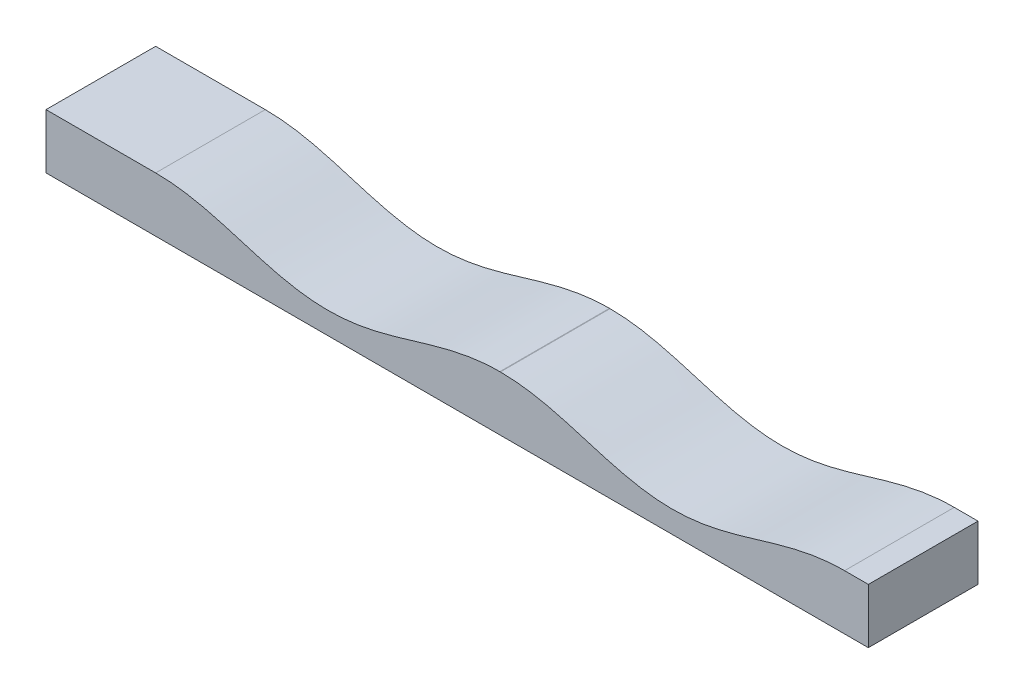
SolidWorks part; units mm, degrees
ref_plane "Front Plane" through (0, 0, 0) normal (0, 0, 1) x (1, 0, 0)
ref_plane "Top Plane" through (0, 0, 0) normal (0, 1, 0) x (1, 0, 0)
ref_plane "Right Plane" through (0, 0, 0) normal (1, 0, 0) x (0, 0, -1)
sketch "Sketch1" plane through (0, 0, 0) normal (0, 1, 0) x (1, 0, 0)
  line L1 (150, -10) -> (0, -10)
  line L2 (150, -10) -> (150, 10)
  line L3 (150, 10) -> (0, 10)
  line L4 (0, -10) -> (0, 10)
  line L5 (150, -10) -> (0, 10) construction
  line L6 (150, 10) -> (0, -10) construction
  point P0 (75, 0)
  point P5 (0, 0)
  dimension "D1" = 20
  dimension "D2" = 150
extrude "Boss-Extrude1" add sketch "Sketch1" along normal blind 10
sketch "Sketch2" plane through (0, 0, 0) normal (0, 0, 1) x (1, 0, 0)
  line L0 (0, 10) -> (20, 10) construction
  line L1 (20, 10) -> (145.6637, 10)
  spline S0 degree 4 poles (7.4336, 7.927) (7.8832, 8.0554) (8.7838, 8.3072) (10.1396, 8.6674) (11.7328, 9.0425) (13.1075, 9.3224) (14.3551, 9.5403) (15.3091, 9.6816) (16.199, 9.7903) (17.0227, 9.8706) (17.6834, 9.9225) (18.2645, 9.9568) (18.7489, 9.9781) (19.1768, 9.9904) (19.5397, 9.997) (19.8673, 10.0002) (20.101, 10.0003) (20.3973, 9.9977) (20.715, 9.9926) (21.1006, 9.983) (21.5319, 9.9665) (22.0363, 9.9399) (22.6209, 9.8996) (23.3458, 9.8371) (24.0968, 9.7559) (24.8715, 9.6548) (25.8402, 9.507) (26.6877, 9.3582) (27.5321, 9.1921) (28.3731, 9.0103) (29.0441, 8.8562) (30.1123, 8.5976) (31.5729, 8.2143) (33.4199, 7.6875) (35.6526, 7.0168) (37.7333, 6.3909) (39.6691, 5.8343) (41.8729, 5.2491) (44.6638, 4.6085) (48.2287, 4.0405) (52.5867, 3.881) (57.2015, 4.3771) (61.6874, 5.3848) (65.9249, 6.6292) (69.9775, 7.8735) (74.1046, 8.994) (78.3423, 9.8146) (82.8319, 10.1408) (87.3215, 9.8146) (91.5591, 8.994) (95.6863, 7.8735) (99.7388, 6.6292) (103.9763, 5.3848) (108.4623, 4.3771) (113.077, 3.881) (117.435, 4.0406) (121.4196, 4.6753) (124.7702, 5.4862) (127.5241, 6.2688) (130.0111, 7.0167) (132.2438, 7.6876) (134.2564, 8.2615) (136.0511, 8.7273) (137.6255, 9.0897) (138.9751, 9.3626) (140.2807, 9.5848) (141.3958, 9.7374) (142.3179, 9.8371) (143.0428, 9.8996) (143.6274, 9.9399) (144.1319, 9.9665) (144.5631, 9.983) (144.9487, 9.9926) (145.2664, 9.9977) (145.5627, 10.0003) (145.7964, 10.0002) (146.124, 9.997) (146.4869, 9.9904) (146.9148, 9.9781) (147.3185, 9.9603) (147.7313, 9.9372) (148.1453, 9.9088) (148.4758, 9.8828) (148.8881, 9.8465) (149.547, 9.7803) (150.5867, 9.6533) (152.0017, 9.4318) (153.7033, 9.0961) (155.5241, 8.6674) (156.8799, 8.3072) (157.7805, 8.0554) (158.2301, 7.927) knots 0 0 0 0 0 0.012144 0.024288 0.036432 0.042504 0.048576 0.057179 0.06148 0.065781 0.070082 0.074383 0.076533 0.078684 0.080834 0.082985 0.084877 0.086769 0.088661 0.090554 0.094338 0.098122 0.101907 0.105691 0.11326 0.11773 0.1222 0.131139 0.135609 0.140079 0.144549 0.149019 0.164156 0.179294 0.194432 0.20957 0.220589 0.231609 0.253648 0.283924 0.314199 0.344474 0.373832 0.40319 0.428888 0.454587 0.484862 0.515138 0.545413 0.571112 0.59681 0.626168 0.655526 0.685801 0.716076 0.746352 0.768391 0.79043 0.805568 0.820706 0.835844 0.850981 0.859921 0.868861 0.8778 0.88674 0.894309 0.898093 0.901878 0.905662 0.909446 0.911339 0.913231 0.915123 0.917015 0.919166 0.921316 0.923467 0.925617 0.929918 0.932069 0.934219 0.93637 0.93852 0.942821 0.951424 0.963568 0.975712 0.987856 1 1 1 1 1 construction
  spline S1 degree 4 poles (20, 10) (20.0608, 10) (20.1824, 9.9996) (20.3973, 9.9977) (20.715, 9.9926) (21.1006, 9.983) (21.5319, 9.9665) (22.0363, 9.9399) (22.6209, 9.8996) (23.3458, 9.8371) (24.0968, 9.7559) (24.8715, 9.6548) (25.8402, 9.507) (26.6877, 9.3582) (27.5321, 9.1921) (28.3731, 9.0103) (29.0441, 8.8562) (30.1123, 8.5976) (31.5729, 8.2143) (33.4199, 7.6875) (35.6526, 7.0168) (37.7333, 6.3909) (39.6691, 5.8343) (41.8729, 5.2491) (44.6638, 4.6085) (48.2287, 4.0405) (52.5867, 3.881) (57.2015, 4.3771) (61.6874, 5.3848) (65.9249, 6.6292) (69.9775, 7.8735) (74.1046, 8.994) (78.3423, 9.8146) (82.8319, 10.1408) (87.3215, 9.8146) (91.5591, 8.994) (95.6863, 7.8735) (99.7388, 6.6292) (103.9763, 5.3848) (108.4623, 4.3771) (113.077, 3.881) (117.435, 4.0406) (121.4196, 4.6753) (124.7702, 5.4862) (127.5241, 6.2688) (130.0111, 7.0167) (132.2438, 7.6876) (134.2564, 8.2615) (136.0511, 8.7273) (137.6255, 9.0897) (138.9751, 9.3626) (140.2807, 9.5848) (141.3958, 9.7374) (142.3179, 9.8371) (143.0428, 9.8996) (143.6274, 9.9399) (144.1319, 9.9665) (144.5631, 9.983) (144.9487, 9.9926) (145.2664, 9.9977) (145.4813, 9.9996) (145.6029, 10) (145.6637, 10) knots 0.082985 0.082985 0.082985 0.082985 0.082985 0.084877 0.086769 0.088661 0.090554 0.094338 0.098122 0.101907 0.105691 0.11326 0.11773 0.1222 0.131139 0.135609 0.140079 0.144549 0.149019 0.164156 0.179294 0.194432 0.20957 0.220589 0.231609 0.253648 0.283924 0.314199 0.344474 0.373832 0.40319 0.428888 0.454587 0.484862 0.515138 0.545413 0.571112 0.59681 0.626168 0.655526 0.685801 0.716076 0.746352 0.768391 0.79043 0.805568 0.820706 0.835844 0.850981 0.859921 0.868861 0.8778 0.88674 0.894309 0.898093 0.901878 0.905662 0.909446 0.911339 0.913231 0.915123 0.917015 0.917015 0.917015 0.917015 0.917015
  dimension "D1" = 20
extrude "Cut-Extrude1" cut sketch "Sketch2" against normal through all both and the other way through all
